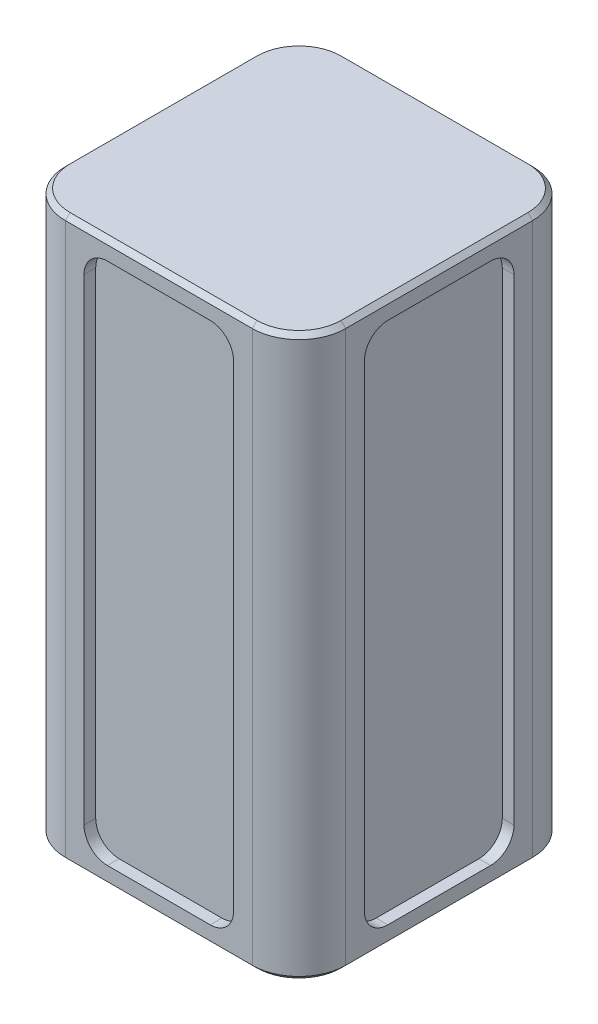
SolidWorks part; units mm, degrees
ref_plane "Front Plane" through (0, 0, 0) normal (0, 0, 1) x (1, 0, 0)
ref_plane "Top Plane" through (0, 0, 0) normal (0, 1, 0) x (1, 0, 0)
ref_plane "Right Plane" through (0, 0, 0) normal (1, 0, 0) x (0, 0, -1)
sketch "Sketch1" plane through (0, 0, 0) normal (0, 1, 0) x (1, 0, 0)
  line L1 (-65.2809, -14.1573) -> (-25.2809, -14.1573)
  line L2 (-75.2809, -4.1573) -> (-75.2809, 35.8427)
  line L3 (-65.2809, 45.8427) -> (-25.2809, 45.8427)
  line L4 (-15.2809, -4.1573) -> (-15.2809, 35.8427)
  arc A0 (-65.2809, -14.1573) -> (-75.2809, -4.1573) centre (-65.2809, -4.1573) cw
  arc A1 (-25.2809, -14.1573) -> (-15.2809, -4.1573) centre (-25.2809, -4.1573) ccw
  arc A2 (-25.2809, 45.8427) -> (-15.2809, 35.8427) centre (-25.2809, 35.8427) cw
  arc A3 (-75.2809, 35.8427) -> (-65.2809, 45.8427) centre (-65.2809, 35.8427) cw
  circle A4 centre (-45.2809, 15.8427) radius 25
  point P6 (-75.2809, -14.1573)
  point P11 (-15.2809, 45.8427)
  point P14 (-75.2809, 45.8427)
  dimension "D3" = 10
  dimension "D4" = 50
  dimension "D1" = 60
  dimension "D2" = 60
extrude "Boss-Extrude1" add sketch "Sketch1" along normal blind 20 contours L2 A3 L3 A2 L4 A1 L1 A0
extrude "Boss-Extrude2" add sketch "Sketch1<3>" against normal blind 100
sketch "Sketch1<3>" plane through (0, 0, 0) normal (0, 1, 0) x (1, 0, 0) same geometry as "Sketch1"
sketch "Sketch2" plane through (0, 0, -45.8427) normal (0, 0, -1) x (-1, 0, 0)
  line L0 (61.2809, -91) -> (61.2809, 11)
  line L1 (56.2809, 16) -> (34.2809, 16)
  line L2 (29.2809, 11) -> (29.2809, -91)
  line L3 (34.2809, -96) -> (56.2809, -96)
  line L8 (65.2809, -100) -> (65.2809, 20)
  line L9 (65.2809, 20) -> (25.2809, 20)
  line L10 (25.2809, 20) -> (25.2809, -100)
  line L11 (25.2809, -100) -> (65.2809, -100)
  line L12 (29.2809, 16) -> (29.2809, -96) construction
  line L13 (29.2809, -96) -> (61.2809, -96) construction
  line L14 (61.2809, -96) -> (61.2809, 16) construction
  line L15 (61.2809, 16) -> (29.2809, 16) construction
  line L17 (25.2809, -100) -> (65.2809, -100) construction
  arc A0 (29.2809, -91) -> (34.2809, -96) centre (34.2809, -91) ccw
  arc A1 (61.2809, -91) -> (56.2809, -96) centre (56.2809, -91) cw
  arc A2 (61.2809, 11) -> (56.2809, 16) centre (56.2809, 11) ccw
  arc A3 (34.2809, 16) -> (29.2809, 11) centre (34.2809, 11) ccw
  dimension "D3" = 5
  dimension "D2" = 4
extrude "Cut-Extrude1" cut sketch "Sketch2" against normal blind 2.5 contours A3 L2 A0 L3 A1 L0 A2 L1
pattern_circular "CirPattern1" count 4 over 360 about axis through (-45.2809, -100, -15.8427) along (0, 1, 0) of "Cut-Extrude1"
chamfer "Chamfer1" distance 1 angle 45 17 edges at (-45.2809, -100, 9.1573) (-75.2809, -100, -15.8427) (-72.352, -100, -42.9138) (-45.2809, -100, -45.8427) (-18.2098, -100, -42.9138) (-15.2809, -100, -15.8427) (-18.2098, -100, 11.2284) (-45.2809, -100, 14.1573) (-72.352, -100, 11.2284) (-18.2098, 20, 11.2284) (-18.2098, 20, -42.9138) (-72.352, 20, -42.9138) (-72.352, 20, 11.2284) (-45.2809, 20, -45.8427) (-15.2809, 20, -15.8427) (-45.2809, 20, 14.1573) (-75.2809, 20, -15.8427)
